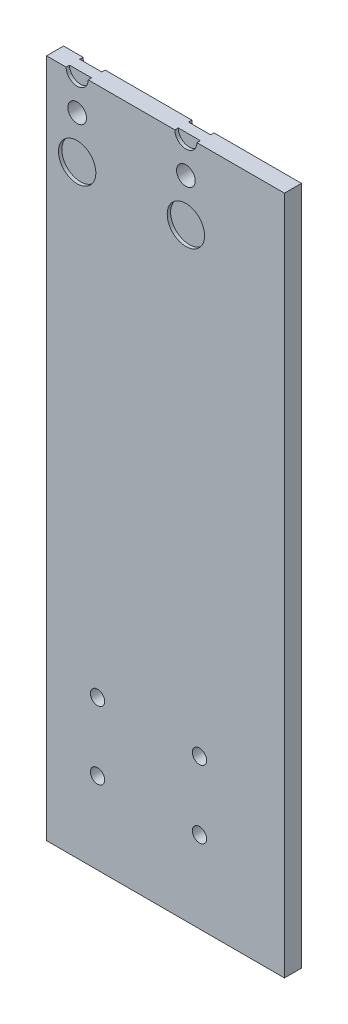
SolidWorks part; units mm, degrees
ref_plane "정면" through (0, 0, 0) normal (0, 0, 1) x (1, 0, 0)
ref_plane "윗면" through (0, 0, 0) normal (0, 1, 0) x (1, 0, 0)
ref_plane "우측면" through (0, 0, 0) normal (1, 0, 0) x (0, 0, -1)
sketch "스케치1" plane through (0, 0, 0) normal (0, 0, 1) x (1, 0, 0)
  line L1 (-50, 100) -> (50, 100)
  line L2 (-50, 100) -> (-50, -100)
  line L3 (-50, -100) -> (50, -100)
  line L4 (50, 100) -> (50, -100)
  line L5 (-50, 100) -> (50, -100) construction
  line L6 (-50, -100) -> (50, 100) construction
  point P0 (0, 0)
  dimension "D1" = 100
  dimension "D2" = 200
extrude "보스-돌출1" add sketch "스케치1" along normal blind 5
sketch "스케치3" plane through (0, 0, 0) normal (0, 0, -1) x (-1, 0, 0)
  text T0 "front"
extrude "컷-돌출2" cut sketch "스케치3" against normal blind 0.001
ref_plane "평면1" through (0, 0, -5) normal (0, 0, -1) x (-1, 0, 0)
hole_wizard "M4x0.7 Helicoil용 탭 구멍1" positions "스케치10" profile "스케치11" tap size "M4x0.7" standard "Helicoil® Metric" end condition through all
sketch "스케치10" plane through (0, 0, -5) normal (0, 0, -1) x (-1, 0, 0)
  line L0 (50, -100) -> (-50, -100) construction
  line L1 (-50, -100) -> (-50, 100) construction
  line L2 (50, 100) -> (50, -100) construction
  point P0 (-5, -76)
  point P2 (25, -76)
  point P4 (-5, -56)
  point P6 (25, -56)
  dimension "D1" = 24
  dimension "D2" = 24
  dimension "D3" = 45
  dimension "D4" = 25
  dimension "D5" = 25
  dimension "D6" = 45
  dimension "D7" = 20
  dimension "D8" = 20
sketch "스케치11" plane through (5, -76, -5) normal (1, 0, 0) x (0, 1, 0)
  line L0 (0, 0) -> (0, 10)
  line L1 (0, 10) -> (2.1, 10)
  line L2 (2.1, 10) -> (2.1, 0)
  line L5 (2.1, 0) -> (0, 0)
  line L11 (0, -6.35) -> (0, 107.95) construction
  dimension "관통 탭 드릴 지름" = 4.2
  dimension "관통 탭 드릴 깊이" = 10
cosmetic thread "구멍 나사산1" parameters "D1"=4.7, "D2"=5.007
cosmetic thread "구멍 나사산2" parameters "D1"=4.7, "D2"=5.007
cosmetic thread "구멍 나사산3" parameters "D1"=4.7, "D2"=5.007
cosmetic thread "구멍 나사산4" parameters "D1"=4.7, "D2"=5.007
sketch "스케치13" plane through (0, 0, 5) normal (0, 0, 1) x (1, 0, 0)
  line L0 (-50, -100) -> (50, -100) construction
  line L1 (50, 100) -> (40, 100)
  line L2 (50, 100) -> (50, -100)
  line L3 (50, -100) -> (40, -100)
  line L4 (40, 100) -> (40, -100)
  line L5 (0, -2.75) -> (0, 2.75) construction
  line L6 (-40, 100) -> (-40, -100)
  line L7 (-50, -100) -> (-40, -100)
  line L8 (-50, 100) -> (-50, -100)
  line L9 (-50, 100) -> (-40, 100)
  dimension "D1" = 10
extrude "컷-돌출4" cut sketch "스케치13" against normal blind 10
sketch "스케치14" plane through (0, 0, 5) normal (0, 0, 1) x (1, 0, 0)
  line L0 (-40, -100) -> (40, -100) construction
  line L1 (40, 100) -> (30, 100)
  line L2 (40, 100) -> (40, -100)
  line L3 (40, -100) -> (30, -100)
  line L4 (30, 100) -> (30, -100)
  dimension "D1" = 10
extrude "컷-돌출5" cut sketch "스케치14" against normal blind 10
sketch "스케치15" plane through (0, 0, 5) normal (0, 0, -1) x (-1, 0, 0)
  line L0 (-30, 100) -> (40, 100) construction
  line L2 (40, -100) -> (40, 100) construction
  circle A0 centre (-1, 100) radius 3.25
  circle A1 centre (31, 100) radius 3.25
  circle A2 centre (-1, 77.4) radius 5.5
  circle A3 centre (31, 77.4) radius 5.5
  dimension "D1" = 11
  dimension "D2" = 11
  dimension "D3" = 6.5
  dimension "D4" = 6.5
  dimension "D6" = 22.6
  dimension "D7" = 9
  dimension "D8" = 9
  dimension "D5" = 22.6
  dimension "D9" = 41
  dimension "D10" = 41
extrude "컷-돌출6" cut sketch "스케치15" along normal blind 1
sketch "스케치16" plane through (0, 0, 0) normal (0, 0, -1) x (-1, 0, 0)
  line L1 (-30, 100) -> (40, 100) construction
  line L2 (40, -100) -> (40, 100) construction
  circle A0 centre (-1, 90) radius 2.75
  circle A1 centre (31, 90) radius 2.75
  dimension "D1" = 5.5
  dimension "D2" = 9
  dimension "5.5" = 5.5
  dimension "D4" = 10
  dimension "D5" = 10
  dimension "D3" = 41
extrude "컷-돌출7" cut sketch "스케치16" against normal through all
ref_plane "평면2" through (0, 0, 2.5) normal (0, 0, 1) x (1, 0, 0)
mirror "대칭 복사1" about plane through (0, 0, 2.5) normal (0, 0, 1) of "컷-돌출6"
